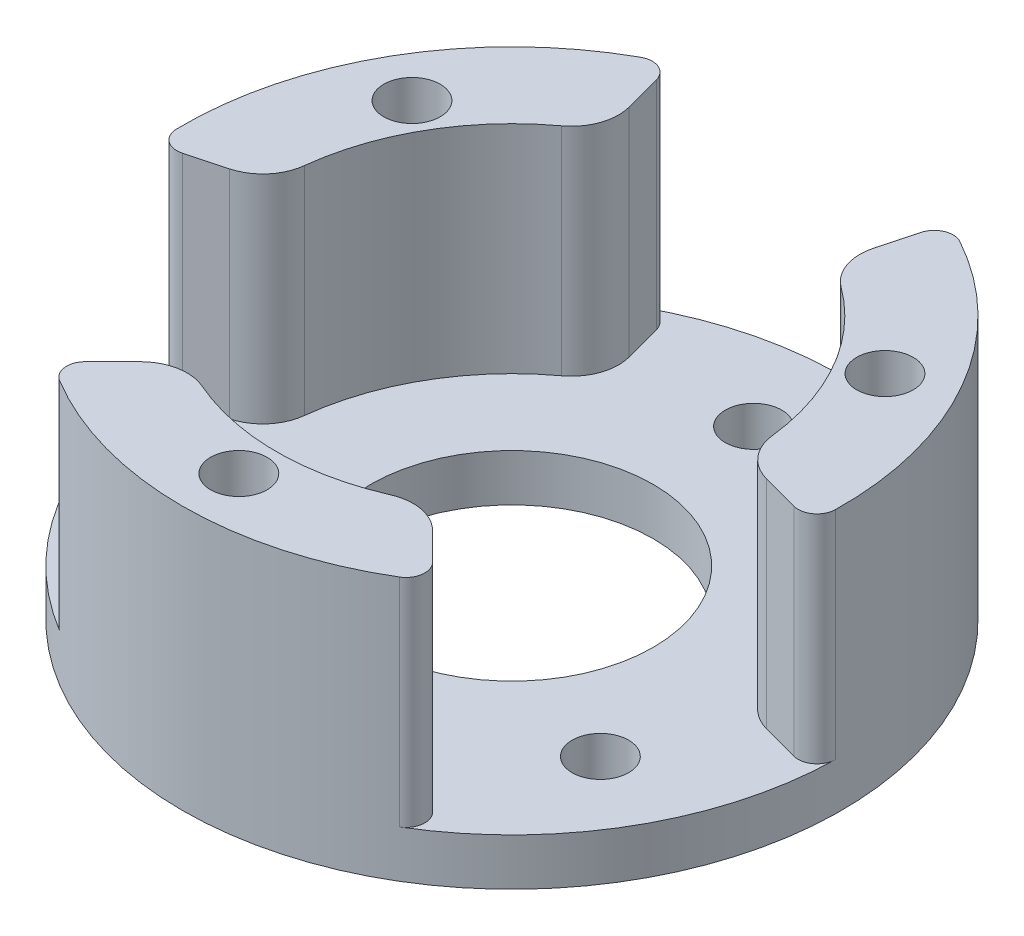
SolidWorks part; units mm, degrees
ref_plane "Front Plane" through (0, 0, 0) normal (0, 0, 1) x (1, 0, 0)
ref_plane "Top Plane" through (0, 0, 0) normal (0, 1, 0) x (1, 0, 0)
ref_plane "Right Plane" through (0, 0, 0) normal (1, 0, 0) x (0, 0, -1)
sketch "Sketch1" plane through (0, 0, 0) normal (0, 1, 0) x (1, 0, 0)
  line L0 (0, 25.66) -> (0, 0) construction
  line L1 (22.2222, -12.83) -> (0, 0) construction
  line L2 (-22.2222, -12.83) -> (0, 0) construction
  circle A0 centre (0, 0) radius 25.66 construction
  circle A1 centre (0, 0) radius 35
  circle A2 centre (0, 25.66) radius 3
  circle A3 centre (22.2222, -12.83) radius 3
  circle A4 centre (-22.2222, -12.83) radius 3
  circle A5 centre (0, 0) radius 15
  point P3 (0, 25.66)
  point P7 (22.2222, -12.83)
  point P9 (-22.2222, -12.83)
  point P11 (0, 0)
  point P18 (0, 0)
  dimension "D3" = 70
  dimension "D4" = 6
  dimension "D6" = 30
  dimension "D2" = 25.66
  dimension "D1" = 3
  dimension "D5" = 3
extrude "Boss-Extrude1" add sketch "Sketch1" along normal blind 5
sketch "Sketch2" plane through (0, 5, 0) normal (0, -1, 0) x (1, 0, 0)
  line L0 (0, 0) -> (0, 35) construction
  line L1 (15.5355, 23.9599) -> (20.1755, 28.5998)
  line L2 (-15.5355, 23.9599) -> (-20.1755, 28.5998)
  line L3 (28.5177, 1.4742) -> (34.8559, 3.1725)
  line L4 (12.9821, -25.4341) -> (14.6805, -31.7724)
  line L5 (-12.9821, -25.4341) -> (-14.6805, -31.7724)
  line L6 (-28.5177, 1.4742) -> (-34.8559, 3.1725)
  circle A0 centre (0, 0) radius 35 construction
  arc A1 (-20.1755, 28.5998) -> (20.1755, 28.5998) centre (0, 0) cw
  arc A2 (-10, 22.9129) -> (10, 22.9129) centre (0, 0) cw
  arc A3 (10, 22.9129) -> (15.5355, 23.9599) centre (12, 27.4955) ccw
  arc A4 (-10, 22.9129) -> (-15.5355, 23.9599) centre (-12, 27.4955) cw
  arc A5 (24.8431, -2.7962) -> (28.5177, 1.4742) centre (29.8118, -3.3554) cw
  arc A6 (34.8559, 3.1725) -> (14.6805, -31.7724) centre (0, 0) cw
  arc A7 (14.8431, -20.1167) -> (12.9821, -25.4341) centre (17.8118, -24.14) ccw
  arc A8 (24.8431, -2.7962) -> (14.8431, -20.1167) centre (0, 0) cw
  arc A9 (-14.8431, -20.1167) -> (-12.9821, -25.4341) centre (-17.8118, -24.14) cw
  arc A10 (-14.6805, -31.7724) -> (-34.8559, 3.1725) centre (0, 0) cw
  arc A11 (-24.8431, -2.7962) -> (-28.5177, 1.4742) centre (-29.8118, -3.3554) ccw
  arc A12 (-14.8431, -20.1167) -> (-24.8431, -2.7962) centre (0, 0) cw
  point P33 (0, 0)
  dimension "D1" = 5
  dimension "D2" = 25
  dimension "D3" = 45
  dimension "D4" = 20
  dimension "D5" = 3
extrude "Pegs" add sketch "Sketch2" against normal blind 22.9915
fillet "Fillet1" radius 2 6 edges at (-34.8559, 16.4958, 3.1725) (-14.6805, 16.4958, -31.7724) (14.6805, 16.4958, -31.7724) (34.8559, 16.4958, 3.1725) (20.1755, 16.4958, 28.5998) (-20.1755, 16.4958, 28.5998)
sketch "Sketch3" plane through (0, 0, 0) normal (0, -1, 0) x (1, 0, 0)
  line L0 (0, 0) -> (0, 29) construction
  line L1 (0, 0) -> (25.1147, -14.5) construction
  line L2 (0, 0) -> (-25.1147, -14.5) construction
  circle A0 centre (0, 0) radius 29 construction
  point P4 (0, 29)
  point P5 (25.1147, -14.5)
  point P7 (-25.1147, -14.5)
  point P8 (0, 0)
  dimension "D1" = 58
  dimension "D2" = 3
hole_wizard "Ø6.0mm Dowel Hole2" positions "Sketch3" profile "Sketch4" hole size "Ø6.0" standard "ANSI Metric" end condition through all
sketch "Sketch4" plane through (-25.1147, 0, -14.5) normal (1, 0, 0) x (0, 0, -1)
  line L0 (0, 0) -> (0, 27.9915)
  line L1 (0, 27.9915) -> (3, 27.9915)
  line L2 (3, 27.9915) -> (3, 0)
  line L5 (3, 0) -> (0, 0)
  line L11 (0, -6.35) -> (0, 107.95) construction
  dimension "Thru Hole Dia." = 6
  dimension "Thru Hole Depth" = 27.9915
